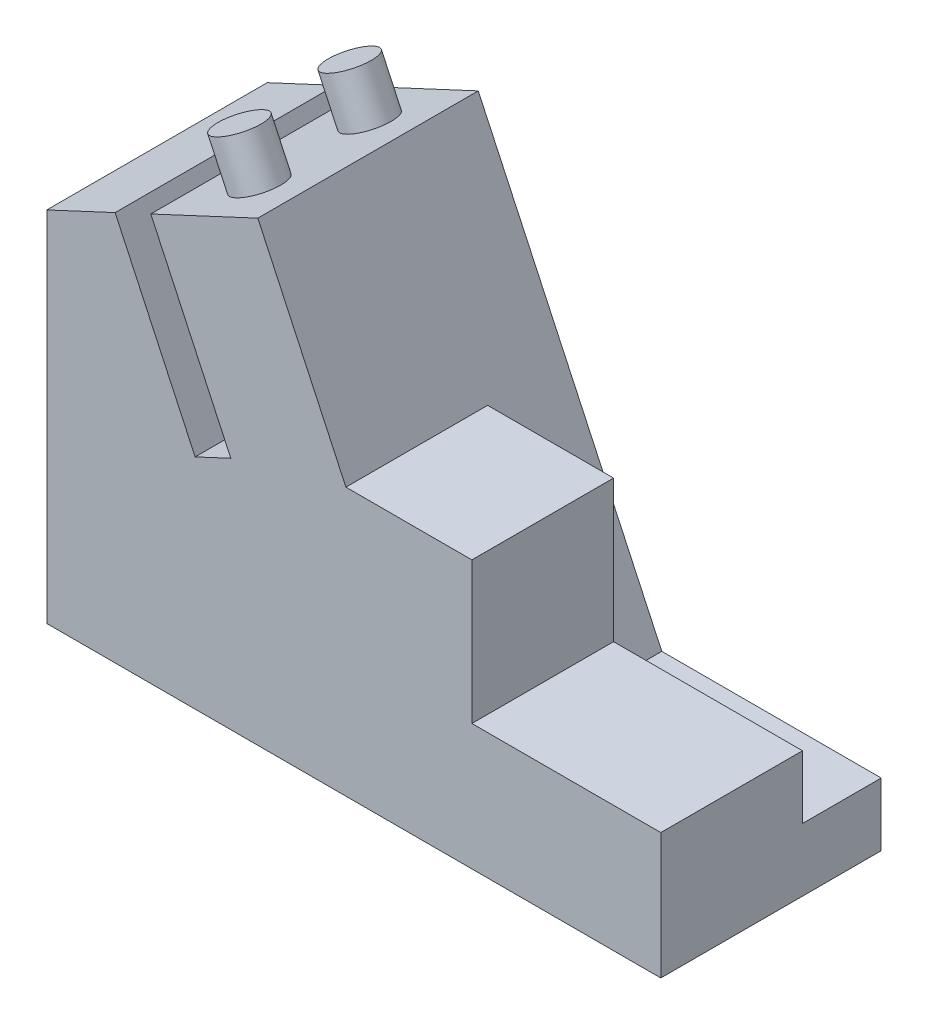
SolidWorks part; units mm, degrees
ref_plane "Front Plane" through (0, 0, 0) normal (0, 0, 1) x (1, 0, 0)
ref_plane "Top Plane" through (0, 0, 0) normal (0, 1, 0) x (1, 0, 0)
ref_plane "Right Plane" through (0, 0, 0) normal (1, 0, 0) x (0, 0, -1)
sketch "Sketch1" plane through (0, 0, 0) normal (0, 0, 1) x (1, 0, 0)
  line L0 (0, 0) -> (-78, 0)
  line L1 (0, 0) -> (0, 8)
  line L2 (0, 8) -> (0, 16)
  line L3 (0, 16) -> (-24, 16)
  line L4 (-24, 16) -> (-24, 34)
  line L5 (-24, 34) -> (-40, 34)
  line L6 (-40, 34) -> (-27.876, 8)
  line L7 (-27.876, 8) -> (0, 8)
  line L8 (-40, 34) -> (-51.1914, 58) construction
  line L9 (-51.1914, 58) -> (-64.786, 51.6607)
  line L10 (-64.786, 51.6607) -> (-54.6227, 29.8654)
  line L11 (-54.6227, 29.8654) -> (-59.1542, 27.7523)
  line L12 (-59.1542, 27.7523) -> (-69.3175, 49.5476)
  line L13 (-78, 0) -> (-78, 45.6144)
  line L14 (-69.3175, 49.5476) -> (-78, 45.4989)
  line L15 (-51.1914, 58) -> (-40, 34)
  dimension "D1" = 24
  dimension "D2" = 16
  dimension "D3" = 65
  dimension "D4" = 8
  dimension "D5" = 8
  dimension "D6" = 18
  dimension "D7" = 58
  dimension "D8" = 15
  dimension "D9" = 78
extrude "Boss-Extrude1" add sketch "Sketch1" against normal blind 18 contours L6 L7 L2 L3 L4 L5 region at (-13.938, 8.4771, 0)
ref_plane "Plane1" through (-40, 34, 0) normal (0.4226, -0.9063, 0) x (-0.9063, -0.4226, 0)
extrude "Boss-Extrude2" add sketch "Sketch1<4>" against normal blind 28 contours L15 L9 L10 L11 L12 L14 L13 L0 L1 L7 L6 region at (-51.8726, 20.9395, 0)
sketch "Sketch1<4>" plane through (0, 0, 0) normal (0, 0, 1) x (1, 0, 0) same geometry as "Sketch1"
sketch "Sketch4" plane through (-31.3584, 67.2483, 0) normal (-0.4226, 0.9063, 0) x (0.9063, 0.4226, 0)
  line L0 (-21.8833, 28) -> (-36.8833, 28) construction
  line L1 (-36.8833, 28) -> (-36.8833, 0) construction
  line L2 (-21.8833, 0) -> (-36.8833, 0) construction
  circle A0 centre (-29.3833, 7) radius 3
  circle A1 centre (-29.3833, 21) radius 3
  dimension "D1" = 7
  dimension "D2" = 7.5
  dimension "D3" = 0
  dimension "D4" = 7
extrude "Boss-Extrude3" add sketch "Sketch4" along normal blind 6
